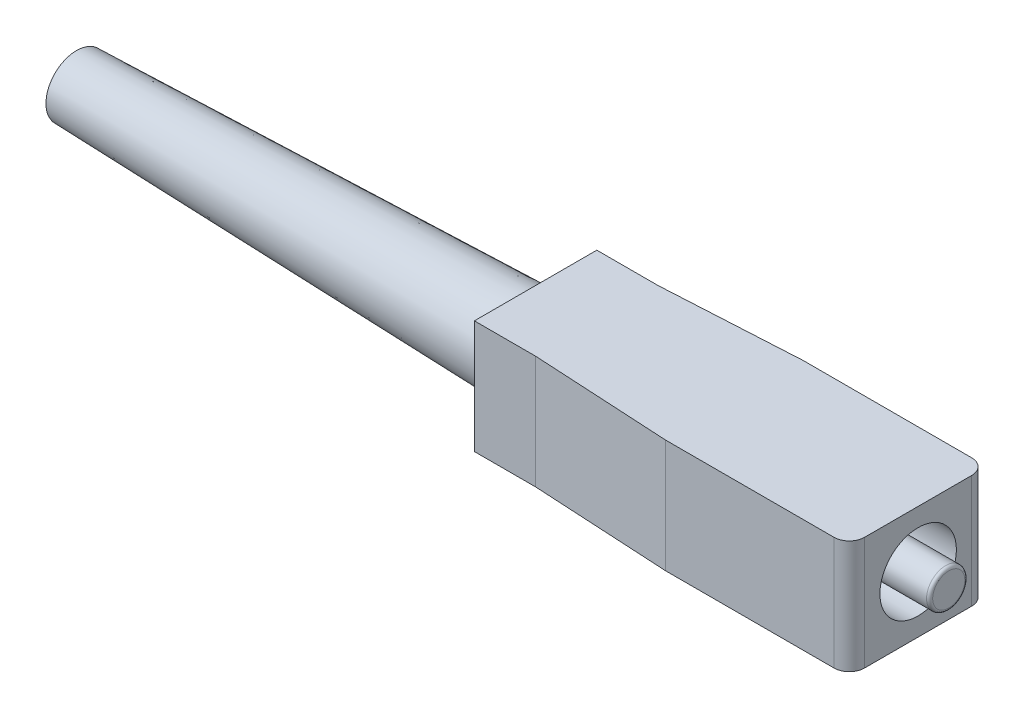
SolidWorks part; units mm, degrees
ref_plane "前视基准面" through (0, 0, 0) normal (0, 0, 1) x (1, 0, 0)
ref_plane "上视基准面" through (0, 0, 0) normal (0, 1, 0) x (1, 0, 0)
ref_plane "右视基准面" through (0, 0, 0) normal (1, 0, 0) x (0, 0, -1)
sketch "草图2" plane through (0, 0, 0) normal (0, 1, 0) x (1, 0, 0)
  line L0 (-64.427, 0) -> (63.4458, 0) construction
  line L1 (0, -39.77) -> (0, 34.1055) construction
  line L2 (12, 4.5) -> (12, -4.5)
  line L3 (12, -4.5) -> (0, -4.5)
  line L4 (0, -4.5) -> (-9, -4)
  line L5 (-9, -4) -> (-13, -4)
  line L6 (-13, -4) -> (-13, 4)
  line L7 (-9, 4) -> (-13, 4)
  line L8 (0, 4.5) -> (-9, 4)
  line L9 (12, 4.5) -> (0, 4.5)
  point P9 (-13, 0)
  point P15 (12, 0)
  dimension "D1" = 9
  dimension "D2" = 12
  dimension "D3" = 4
  dimension "D4" = 25
  dimension "D5" = 8
extrude "凸台-拉伸1" add sketch "草图2" along normal blind 3.7 and the other way blind 3.7
sketch "草图3" plane through (12, 0, 0) normal (1, 0, 0) x (0, 0, -1)
  circle A0 centre (0, 0) radius 2.5
  dimension "D1" = 5
extrude "切除-拉伸1" cut sketch "草图3" against normal blind 5
sketch "草图4" plane through (7, 0, 0) normal (1, 0, 0) x (0, 0, -1)
  circle A0 centre (0, 0) radius 1.25
  dimension "D1" = 2.5
extrude "凸台-拉伸2" add sketch "草图4" along normal offset from surface (7 mm away) 2 up to face at (12, 0, -2.5) offset beyond the face yes
fillet "圆角1" radius 1 2 edges at (12, 0, -4.5) (12, 0, 4.5)
fillet "圆角2" radius 0.2 1 edges at (14, 0, -1.25)
sketch "草图5" plane through (0, 0, 0) normal (0, 1, 0) x (1, 0, 0)
  line L0 (5.4843, 0) -> (-42.7999, 0) construction
  line L1 (-13, 2.9) -> (-43, 2)
  line L2 (-13, 4) -> (-13, -4) construction
  line L3 (-43, 2) -> (-43, 0)
  line L4 (-13, 2.9) -> (-13, 0)
  line L5 (-13, 0) -> (-43, 0)
  dimension "D1" = 2
  dimension "D2" = 2.9
  dimension "D3" = 30
revolve "旋转1" add sketch "草图5" angle 360 about L0
